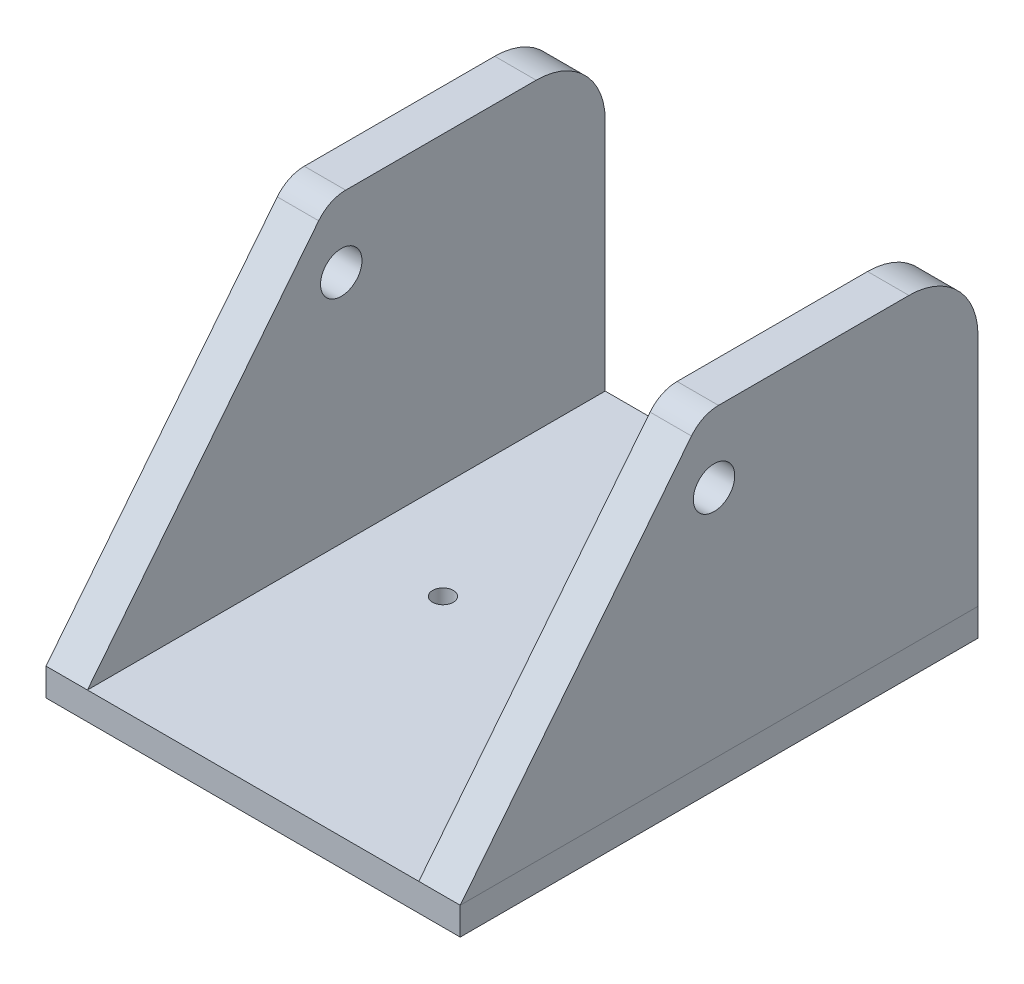
SolidWorks part; units mm, degrees
ref_plane "Front Plane" through (0, 0, 0) normal (0, 0, 1) x (1, 0, 0)
ref_plane "Top Plane" through (0, 0, 0) normal (0, 1, 0) x (1, 0, 0)
ref_plane "Right Plane" through (0, 0, 0) normal (1, 0, 0) x (0, 0, -1)
sketch "Sketch1" plane through (0, 0, 0) normal (0, 1, 0) x (1, 0, 0)
  line L0 (30, 0) -> (-30, 0)
  line L1 (-30, 0) -> (-30, 75)
  line L2 (-30, 75) -> (30, 75)
  line L3 (0, 0) -> (0, 87.606) construction
  line L4 (30, 0) -> (30, 75)
  point P9 (0, 75)
extrude "Boss-Extrude1" add sketch "Sketch1" along normal blind 4
sketch "Sketch2" plane through (0, 4, 0) normal (0, 1, 0) x (1, 0, 0)
  line L0 (-30, 37.5) -> (30, 37.5)
  line L1 (-30, 75) -> (-30, 0) construction
  line L2 (30, 0) -> (30, 75) construction
  line L3 (0, 37.5) -> (10, 37.5)
  line L4 (10, 37.5) -> (-10, 37.5)
  circle A0 centre (-10, 37.5) radius 1.5
  circle A1 centre (10, 37.5) radius 1.5
extrude "Cut-Extrude1" cut sketch "Sketch2" against normal blind 4 and the other way through all contours A0 | A1
sketch "Sketch3" plane through (0, 4, 0) normal (0, 1, 0) x (1, 0, 0)
  line L0 (-30, 75) -> (-24, 75)
  line L1 (30, 75) -> (-30, 75) construction
  line L2 (30, 75) -> (24, 75)
  line L3 (-24, 75) -> (-24, 0)
  line L4 (-30, 0) -> (30, 0) construction
  line L5 (-24, 0) -> (-30, 0)
  line L6 (-30, 0) -> (-30, 75)
  line L7 (24, 75) -> (24, 0)
  line L8 (24, 0) -> (30, 0)
  line L9 (30, 0) -> (30, 75)
  line L10 (-30, 75) -> (-24, 75)
  line L11 (-24, 75) -> (-24, 0)
  line L12 (-24, 0) -> (-30, 0)
  line L13 (-30, 0) -> (-30, 75)
  line L14 (30, 0) -> (30, 75)
  line L15 (-30, 75) -> (-24, 75)
  line L16 (-24, 75) -> (-24, 0)
  line L17 (-24, 0) -> (-30, 0)
  line L18 (-30, 0) -> (-30, 75)
  line L19 (30, 0) -> (30, 75)
  dimension "D1" = 6
  dimension "D2" = 6
ref_plane "Plane1" through (0, 48, 0) normal (0, 1, 0) x (1, 0, 0)
sketch "Sketch4" plane through (0, 48, 0) normal (0, 1, 0) x (1, 0, 0)
  line L7 (24, 75) -> (24, 35)
  line L9 (24, 75) -> (24, 0) construction
  line L12 (24, 35) -> (30, 35)
  line L13 (30, 0) -> (30, 75) construction
  line L14 (30, 0) -> (29.9099, -0.2435)
  line L15 (30, 35) -> (30, 75)
  line L16 (30, 75) -> (24, 75)
  line L17 (-24, 75) -> (-24, 35)
  line L18 (-24, 75) -> (-24, 0) construction
  line L19 (-24, 35) -> (-30, 35)
  line L20 (-30, 0) -> (-30, 75) construction
  line L21 (-30, 35) -> (-30, 75)
  line L22 (-30, 75) -> (-24, 75)
  dimension "D1" = 40
ref_plane "Plane2" through (0, 38, 0) normal (0, 1, 0) x (1, 0, 0)
sketch "Sketch5" plane through (0, 38, 0) normal (0, 1, 0) x (1, 0, 0)
  line L0 (42.8778, 36.7666) -> (-35.6291, 36.7666) construction
  point P3 (42.8778, 36.7666)
  point P4 (-35.2749, 36.7666)
loft "Loft1" add section "Sketch3" section "Sketch4" connector at (30, 4, 0) connector at (30, 48, -35)
loft "Loft2" add section "Sketch3<19>" section "Sketch4<17>" connector at (-24, 4, 0) connector at (-24, 48, -35)
sketch "Sketch3<19>" plane through (0, 4, 0) normal (0, 1, 0) x (1, 0, 0) same geometry as "Sketch3"
sketch "Sketch4<17>" plane through (0, 48, 0) normal (0, 1, 0) x (1, 0, 0) same geometry as "Sketch4"
sketch "Sketch8" plane through (-30, 0, 0) normal (-1, 0, 0) x (0, 0, 1)
  circle A0 centre (-36.7666, 38) radius 3
extrude "Cut-Extrude2" cut sketch "Sketch8" against normal blind 74
fillet "Fillet3" radius 5 2 edges
fillet "Fillet4" radius 10 2 edges
ref_plane "Plane5" through (30, 4, 0) normal (1, 0, 0) x (0, 0, -1)
split "Split1" bodies to split 113 resulting bodies 118 119 120 split by face at (-10, 4, -39)
